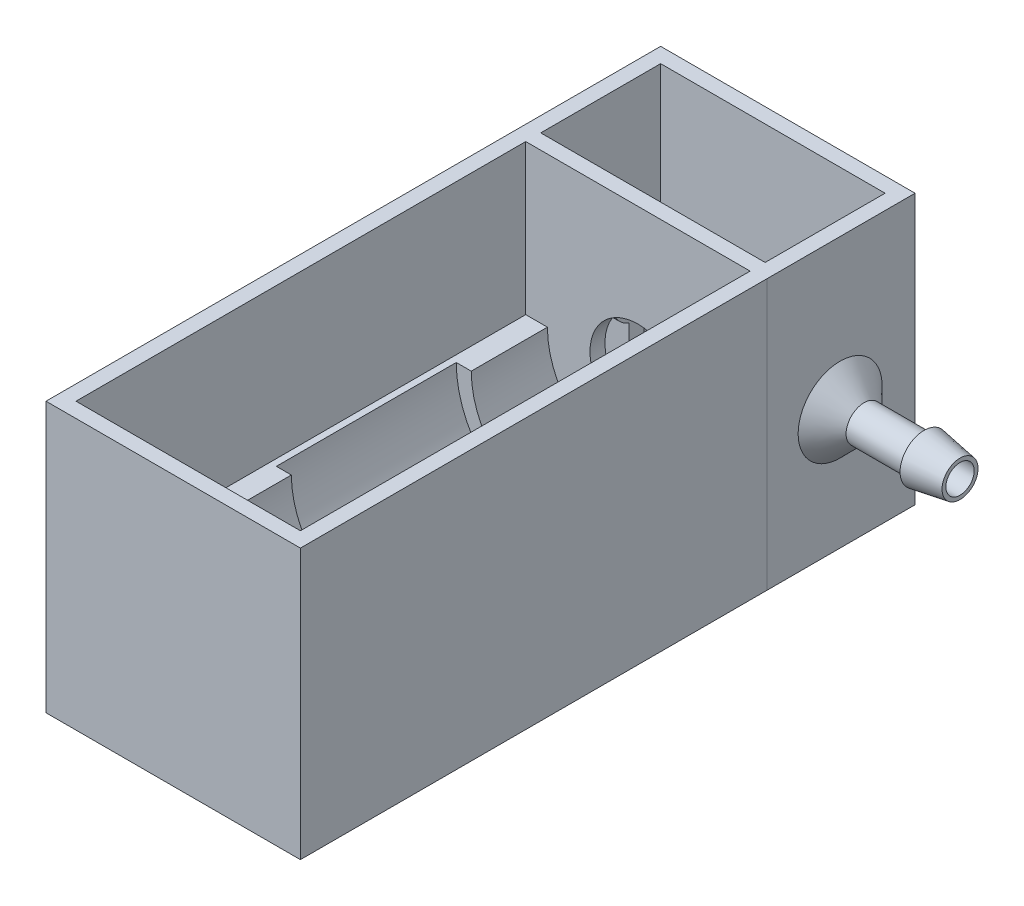
SolidWorks part; units mm, degrees
ref_plane "Front Plane" through (0, 0, 0) normal (0, 0, 1) x (1, 0, 0)
ref_plane "Top Plane" through (0, 0, 0) normal (0, 1, 0) x (1, 0, 0)
ref_plane "Right Plane" through (0, 0, 0) normal (1, 0, 0) x (0, 0, -1)
sketch "Sketch1" plane through (0, 0, 0) normal (0, 0, 1) x (1, 0, 0)
  line L1 (-26.9397, 0) -> (26.9397, 0)
  line L2 (-26.9397, 0) -> (-26.9397, 6.35)
  line L3 (-23.7647, 6.35) -> (23.7647, 6.35)
  line L4 (26.9397, 0) -> (26.9397, 6.35)
  line L6 (-26.9397, 6.35) -> (-26.9397, 57.15)
  line L7 (-26.9397, 57.15) -> (-23.7647, 57.15)
  line L8 (-23.7647, 6.35) -> (-23.7647, 57.15)
  line L10 (26.9397, 6.35) -> (26.9397, 57.15)
  line L11 (26.9397, 57.15) -> (23.7647, 57.15)
  line L12 (23.7647, 6.35) -> (23.7647, 57.15)
  dimension "D1" = 3.175
  dimension "D2" = 53.8795
  dimension "D3" = 6.35
  dimension "D4" = 50.8
extrude "Boss-Extrude1" add sketch "Sketch1" along normal mid plane 25.4
sketch "Sketch2" plane through (0, 0, -12.7) normal (0, 0, -1) x (-1, 0, 0)
  line L0 (26.9397, 0) -> (-26.9397, 0) construction
  line L1 (-26.9397, 57.15) -> (26.9397, 57.15)
  line L2 (-26.9397, 57.15) -> (-26.9397, 0)
  line L3 (-26.9397, 0) -> (26.9397, 0)
  line L4 (26.9397, 57.15) -> (26.9397, 0)
extrude "Boss-Extrude2" add sketch "Sketch2" along normal blind 3.175
sketch "Sketch4" plane through (0, 0, 0) normal (0, 0, 1) x (1, 0, 0)
  line L0 (25.4, 25.4) -> (65.2304, 25.4) construction
  line L1 (0, 25.4) -> (0, 0) construction
  line L2 (52.3397, 26.924) -> (26.9397, 26.924) construction
  line L3 (-32.0197, 29.21) -> (-26.9397, 34.29)
  line L4 (-44.7197, 29.21) -> (-32.0197, 29.21)
  line L5 (-26.9397, 57.15) -> (-26.9397, 0) construction
  line L6 (-44.7197, 29.21) -> (-44.7197, 30.48)
  line L7 (-44.7197, 30.48) -> (-52.3397, 29.21)
  line L8 (-52.3397, 29.21) -> (-52.3397, 26.924)
  line L10 (-26.9397, 26.924) -> (-26.9397, 29.21)
  line L11 (25.4, 25.4) -> (-14.4304, 25.4) construction
  line L12 (26.9397, 34.29) -> (26.9397, 29.21)
  line L13 (26.9397, 25.4) -> (26.9397, 26.924)
  line L14 (52.3397, 25.4) -> (26.9397, 25.4)
  line L15 (52.3397, 26.924) -> (52.3397, 25.4)
  line L16 (-52.3397, 26.924) -> (-52.3397, 25.4)
  line L17 (-52.3397, 25.4) -> (-26.9397, 25.4)
  line L18 (-26.9397, 25.4) -> (-26.9397, 26.924)
  line L19 (26.9397, 26.924) -> (26.9397, 29.21)
  line L20 (52.3397, 29.21) -> (52.3397, 26.924)
  line L21 (44.7197, 30.48) -> (52.3397, 29.21)
  line L22 (44.7197, 29.21) -> (44.7197, 30.48)
  line L23 (-26.9397, 34.29) -> (-26.9397, 29.21)
  line L24 (44.7197, 29.21) -> (32.0197, 29.21)
  line L25 (32.0197, 29.21) -> (26.9397, 34.29)
  point P29 (0, 0)
  dimension "D1" = 3.81
  dimension "D2" = 5.08
  dimension "D3" = 5.08
  dimension "D5" = 45
  dimension "D6" = 25.4
  dimension "D7" = 12.7
  dimension "D8" = 7.62
revolve "Revolve1" add sketch "Sketch4" angle 360 about L0
ref_axis "Axis1" through (-32.0197, 25.4, 0) along (-1, 0, 0)
sketch "Sketch6" plane through (0, 0, 0) normal (0, 0, 1) x (1, 0, 0)
  line L0 (-23.7647, 25.4) -> (-16.1447, 25.4)
  line L3 (-16.1447, 25.4) -> (-16.1447, 30.48)
  line L4 (-16.1447, 30.48) -> (-21.2247, 30.48)
  line L5 (-21.2247, 30.48) -> (-23.7647, 33.02)
  line L6 (0, 25.4) -> (0, 0) construction
  line L7 (-23.7647, 33.02) -> (-23.7647, 25.4)
  line L8 (-32.0197, 25.4) -> (-44.7197, 25.4) construction
  line L9 (-23.7647, 6.35) -> (-23.7647, 57.15) construction
  line L10 (23.7647, 33.02) -> (23.7647, 25.4)
  line L11 (21.2247, 30.48) -> (23.7647, 33.02)
  line L12 (16.1447, 30.48) -> (21.2247, 30.48)
  line L13 (16.1447, 25.4) -> (16.1447, 30.48)
  line L15 (23.7647, 25.4) -> (16.1447, 25.4)
  dimension "D1" = 5.08
  dimension "D2" = 5.08
  dimension "D3" = 7.62
  dimension "D4" = 7.62
revolve "Revolve2" add sketch "Sketch6" angle 360 about L0
sketch "Sketch3" plane through (0, 0, 0) normal (1, 0, 0) x (0, 0, -1)
  circle A0 centre (0, 25.4) radius 3
  dimension "D2" = 6
extrude "Cut-Extrude2" cut sketch "Sketch3" against normal through all both and the other way through all
sketch "Sketch5" plane through (0, 0, 0) normal (0, -1, 0) x (1, 0, 0)
  line L1 (26.9397, -15.875) -> (-26.9397, -15.875)
  line L2 (26.9397, -15.875) -> (26.9397, -41.275)
  line L3 (26.9397, -41.275) -> (-26.9397, -41.275)
  line L4 (-26.9397, -15.875) -> (-26.9397, -41.275)
  circle A0 centre (7.8897, -28.575) radius 3.4925
  circle A1 centre (-17.5103, -28.575) radius 3.4925
  point P9 (26.9397, -28.575)
  dimension "D2" = 6.985
  dimension "D1" = 25.4
  dimension "D3" = 19.05
  dimension "D4" = 2
extrude "Boss-Extrude3" add sketch "Sketch5" against normal blind 6.35
sketch "Sketch7" plane through (0, 0, 0) normal (0, 0, 1) x (1, 0, 0)
  line L0 (23.7647, 6.35) -> (-23.7647, 6.35) construction
  line L1 (-23.7647, 21.9594) -> (-16.1447, 21.9594)
  line L2 (-23.7647, 21.9594) -> (-23.7647, 6.35)
  line L3 (-23.7647, 6.35) -> (-16.1447, 6.35)
  line L4 (-16.1447, 21.9594) -> (-16.1447, 6.35)
  line L5 (-23.7647, 21.9594) -> (-16.1447, 6.35) construction
  line L6 (-23.7647, 6.35) -> (-16.1447, 21.9594) construction
  line L8 (0, 0) -> (0, 25.6446) construction
  line L9 (-26.9397, 0) -> (26.9397, 0) construction
  line L10 (23.7647, 6.35) -> (16.1447, 21.9594) construction
  line L11 (23.7647, 21.9594) -> (16.1447, 6.35) construction
  line L12 (16.1447, 21.9594) -> (16.1447, 6.35)
  line L13 (23.7647, 6.35) -> (16.1447, 6.35)
  line L14 (23.7647, 21.9594) -> (23.7647, 6.35)
  line L15 (23.7647, 21.9594) -> (16.1447, 21.9594)
  line L16 (-23.7647, 6.35) -> (-23.7647, 57.15) construction
  line L17 (-16.1447, 20.32) -> (-16.1447, 30.48) construction
  point P4 (-19.9547, 14.1547)
  point P18 (19.9547, 14.1547)
extrude "Boss-Extrude7" add sketch "Sketch7" along normal mid plane 3.175
sketch "Sketch8" plane through (0, 0, 12.7) normal (0, 0, 1) x (1, 0, 0)
  line L1 (-26.9397, 57.15) -> (26.9397, 57.15)
  line L2 (-26.9397, 57.15) -> (-26.9397, 0)
  line L3 (-26.9397, 0) -> (26.9397, 0)
  line L4 (26.9397, 57.15) -> (26.9397, 0)
  line L5 (-26.9397, 57.15) -> (26.9397, 0) construction
  line L6 (-26.9397, 0) -> (26.9397, 57.15) construction
  point P4 (0, 28.575)
extrude "Boss-Extrude8" add sketch "Sketch8" along normal blind 101.6
sketch "Sketch9" plane through (0, 0, 0) normal (1, 0, 0) x (0, 0, -1)
  line L0 (0, 25.4) -> (-114.3, 25.4) construction
  line L1 (-114.3, 0) -> (-114.3, 57.15) construction
  line L2 (-70.104, 47.752) -> (-70.104, 44.577)
  line L3 (-70.104, 47.752) -> (-32.004, 47.752)
  line L4 (-32.004, 47.752) -> (-32.004, 44.577)
  line L5 (-32.004, 44.577) -> (-20.1041, 44.577)
  line L6 (0, 35.56) -> (0, 25.4)
  line L7 (0, 25.4) -> (12.7, 25.4) construction
  line L8 (12.7, 6.35) -> (12.7, 57.15) construction
  line L9 (0, 25.4) -> (-70.104, 25.4)
  line L10 (-70.104, 44.577) -> (-107.8909, 44.577)
  line L11 (-107.8909, 44.577) -> (-107.8909, 25.4)
  line L12 (-107.8909, 25.4) -> (-70.104, 25.4)
  line L13 (-20.1041, 44.577) -> (-20.1041, 35.56)
  line L14 (-20.1041, 35.56) -> (0, 35.56)
  dimension "D1" = 38.1
  dimension "D2" = 10.16
  dimension "D3" = 22.352
  dimension "D4" = 3.175
revolve "Cut-Revolve1" cut sketch "Sketch9" angle 360 about L9
ref_axis "Axis2" through (0, 25.4, 70.104) along (0, 0, -1)
ref_plane "Plane2" through (0, 25.4, 0) normal (0, 1, 0) x (1, 0, 0)
sketch "Sketch13" plane through (0, 0, 0) normal (0, -1, 0) x (-1, 0, 0)
  line L0 (26.9397, -114.3) -> (26.9397, 41.275) construction
  line L1 (26.9397, -15.4709) -> (26.9421, -15.4709)
  line L2 (26.9397, -15.4709) -> (26.9397, -114.3)
  line L3 (26.9397, -114.3) -> (26.9421, -114.3)
  line L4 (26.9421, -15.4709) -> (26.9421, -114.3)
  line L5 (26.9397, -15.4709) -> (26.9421, -114.3) construction
  line L6 (26.9397, -114.3) -> (26.9421, -15.4709) construction
  line L7 (26.9397, -114.3) -> (-26.9397, -114.3) construction
  line L9 (-26.9397, -114.3) -> (-26.9374, -114.3)
  line L10 (-26.9397, -114.3) -> (-26.9397, -15.4709)
  line L11 (-26.9397, -15.4709) -> (-26.9374, -15.4709)
  line L12 (-26.9374, -114.3) -> (-26.9374, -15.4709)
  line L13 (-26.9397, -114.3) -> (-26.9374, -15.4709) construction
  line L14 (-26.9397, -15.4709) -> (-26.9374, -114.3) construction
  point P4 (26.9409, -64.8855)
  point P13 (-26.9386, -64.8855)
extrude "Cut-Extrude7" cut sketch "Sketch13" against normal through all both and the other way through all
sketch "Sketch14" plane through (0, 57.15, 0) normal (0, 1, 0) x (1, 0, 0)
  line L1 (23.7624, -111.125) -> (-23.7647, -111.125)
  line L2 (23.7624, -111.125) -> (23.7624, -15.875)
  line L3 (23.7624, -15.875) -> (-23.7647, -15.875)
  line L4 (-23.7647, -111.125) -> (-23.7647, -15.875)
  line L5 (23.7624, -111.125) -> (-23.7647, -15.875) construction
  line L6 (23.7624, -15.875) -> (-23.7647, -111.125) construction
  line L7 (26.9374, -114.3) -> (-26.9397, -114.3) construction
  line L8 (26.9374, -114.3) -> (26.9374, -15.4709) construction
  line L10 (23.7647, -12.7) -> (-23.7647, -12.7) construction
  line L11 (-26.9397, -114.3) -> (-26.9397, 15.875) construction
  point P4 (-0.0012, -63.5)
  dimension "D1" = 3.175
  dimension "D2" = 3.175
  dimension "D3" = 3.175
  dimension "D4" = 3.175
extrude "Cut-Extrude8" cut sketch "Sketch14" against normal up to surface (31.75 mm away) up to plane "Plane2"
sketch "Sketch15" plane through (0, 0, 20.1041) normal (0, 0, 1) x (1, 0, 0)
  line L2 (-10.16, 25.4) -> (-19.177, 25.4)
  line L3 (19.177, 25.4) -> (10.16, 25.4)
  line L4 (-10.16, 25.4) -> (-19.177, 25.4)
  line L5 (19.177, 25.4) -> (10.16, 25.4)
  arc A2 (-19.177, 25.4) -> (19.177, 25.4) centre (0, 25.4) ccw
  arc A3 (-10.16, 25.4) -> (10.16, 25.4) centre (0, 25.4) ccw
  arc A4 (-19.177, 25.4) -> (19.177, 25.4) centre (0, 25.4) ccw
  arc A5 (-10.16, 25.4) -> (10.16, 25.4) centre (0, 25.4) ccw
  dimension "D1" = 0
extrude "Cut-Extrude9" cut sketch "Sketch15" against normal up to surface (4.2291 mm away) up to face at (-0.0008, 37.6767, 15.875)
sketch "Sketch16" plane through (0, 6.35, 0) normal (0, 1, 0) x (1, 0, 0)
  line L1 (26.9397, 41.275) -> (-26.9397, 41.275)
  line L2 (26.9397, 41.275) -> (26.9397, 15.875)
  line L3 (26.9397, 15.875) -> (-26.9397, 15.875)
  line L4 (-26.9397, 41.275) -> (-26.9397, 15.875)
  line L5 (26.9397, 41.275) -> (-26.9397, 15.875) construction
  line L6 (26.9397, 15.875) -> (-26.9397, 41.275) construction
  point P4 (0, 28.575)
extrude "Cut-Extrude10" cut sketch "Sketch16" against normal through all
